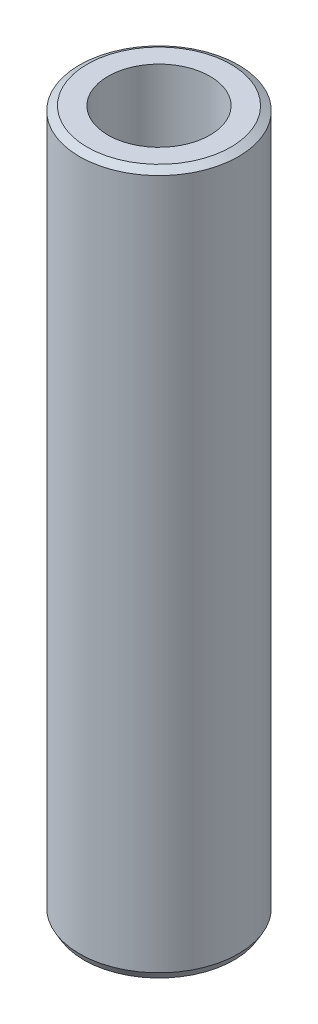
SolidWorks part; units mm, degrees
ref_plane "Front Plane" through (0, 0, 0) normal (0, 0, 1) x (1, 0, 0)
ref_plane "Top Plane" through (0, 0, 0) normal (0, 1, 0) x (1, 0, 0)
ref_plane "Right Plane" through (0, 0, 0) normal (1, 0, 0) x (0, 0, -1)
sketch "Sketch1" plane through (0, 0, 0) normal (0, 1, 0) x (1, 0, 0)
  circle A0 centre (0, 0) radius 45
  dimension "SHAFT_OD" = 90
extrude "Boss-Extrude1" add sketch "Sketch1" along normal blind 397.8053
sketch "Sketch2" plane through (0, 0, 0) normal (0, 1, 0) x (1, 0, 0)
  circle A0 centre (0, 0) radius 28.8872
  dimension "BORE_D" = 57.7743
extrude "Cut-Extrude1" cut sketch "Sketch2" along normal through all
chamfer "Chamfer1" distance 2.4892 angle 60 2 edges at (0, 397.8053, 45) (0, 0, 45) first distance on face at (0, 397.8053, 45) first distance on face at (0, 0, 28.8872)
